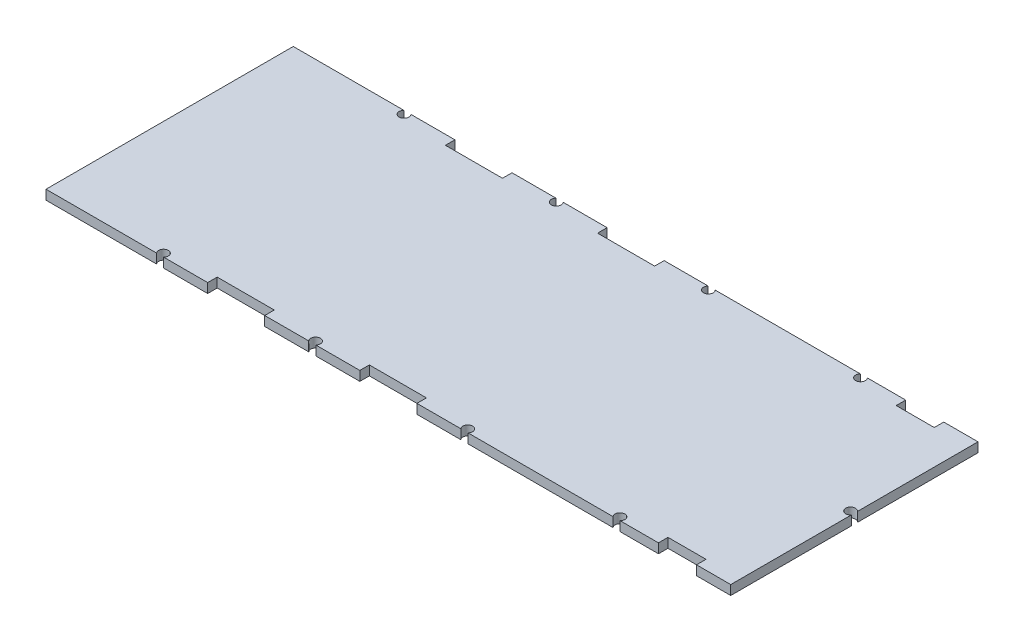
SolidWorks part; units mm, degrees
ref_plane "Front Plane" through (0, 0, 0) normal (0, 0, 1) x (1, 0, 0)
ref_plane "Top Plane" through (0, 0, 0) normal (0, 1, 0) x (1, 0, 0)
ref_plane "Right Plane" through (0, 0, 0) normal (1, 0, 0) x (0, 0, -1)
sketch "Sketch1" plane through (0, 0, 0) normal (0, 1, 0) x (1, 0, 0)
  line L0 (114.3, -1.0072) -> (114.3, -41.275)
  line L1 (-114.3, 41.275) -> (-77.3864, 41.275)
  line L2 (-114.3, 41.275) -> (-114.3, -41.275)
  line L3 (-114.3, -41.275) -> (-77.3864, -41.275)
  line L4 (114.3, 41.275) -> (114.3, 1.0072)
  line L5 (-75.0136, 41.275) -> (-60.325, 41.275)
  line L6 (26.5864, 41.275) -> (75.0136, 41.275)
  line L7 (77.3864, 41.275) -> (89.4932, 41.275)
  line L8 (-24.2136, 41.275) -> (-9.525, 41.275)
  line L9 (-119.8539, 0) -> (200.76, 0) construction
  line L10 (77.3864, -41.275) -> (89.4932, -41.275)
  line L11 (26.5864, -41.275) -> (75.0136, -41.275)
  line L12 (-24.2136, -41.275) -> (-9.525, -41.275)
  line L13 (-75.0136, -41.275) -> (-60.325, -41.275)
  line L14 (-41.275, -41.275) -> (-26.5864, -41.275)
  line L15 (9.525, -41.275) -> (24.2136, -41.275)
  line L16 (-60.325, -41.275) -> (-60.325, -38.1)
  line L17 (-60.325, -38.1) -> (-41.275, -38.1)
  line L18 (-41.275, -41.275) -> (-41.275, -38.1)
  line L19 (-60.325, -43.7685) -> (-41.275, -38.1) construction
  line L20 (-60.325, -38.1) -> (-41.275, -43.7685) construction
  line L21 (102.87, -41.275) -> (114.3, -41.275)
  line L22 (-9.525, -41.275) -> (-9.525, -38.1)
  line L23 (-9.525, -38.1) -> (9.525, -38.1)
  line L24 (9.525, -41.275) -> (9.525, -38.1)
  line L25 (-9.525, -43.7685) -> (9.525, -38.1) construction
  line L26 (-9.525, -38.1) -> (9.525, -43.7685) construction
  line L27 (102.87, 41.275) -> (102.87, 38.1)
  line L28 (89.4932, 41.275) -> (90.17, 41.275)
  line L29 (102.87, 38.1) -> (90.17, 38.1)
  line L30 (102.87, -41.275) -> (102.87, -38.1)
  line L31 (102.87, -38.1) -> (90.17, -38.1)
  line L32 (90.17, -41.275) -> (90.17, -38.1)
  line L33 (90.17, 41.275) -> (90.17, 38.1)
  line L35 (9.525, 41.275) -> (9.525, 38.1)
  line L36 (-9.525, 38.1) -> (9.525, 38.1)
  line L37 (-9.525, 41.275) -> (-9.525, 38.1)
  line L38 (-41.275, 41.275) -> (-41.275, 38.1)
  line L39 (-60.325, 38.1) -> (-41.275, 38.1)
  line L40 (-60.325, 41.275) -> (-60.325, 38.1)
  line L41 (-41.275, 41.275) -> (-26.5864, 41.275)
  line L42 (9.525, 41.275) -> (24.2136, 41.275)
  line L43 (102.87, 41.275) -> (114.3, 41.275)
  line L44 (89.4932, -41.275) -> (90.17, -41.275)
  arc A0 (114.3, 1.0072) -> (114.3, -1.0072) centre (113.024, 0) ccw
  arc A1 (-77.3864, 41.275) -> (-75.0136, 41.275) centre (-76.2, 40.1637) ccw
  arc A2 (-26.5864, 41.275) -> (-24.2136, 41.275) centre (-25.4, 40.1637) ccw
  arc A3 (24.2136, 41.275) -> (26.5864, 41.275) centre (25.4, 40.1637) ccw
  arc A4 (75.0136, 41.275) -> (77.3864, 41.275) centre (76.2, 40.1637) ccw
  arc A5 (75.0136, -41.275) -> (77.3864, -41.275) centre (76.2, -40.1637) cw
  arc A6 (24.2136, -41.275) -> (26.5864, -41.275) centre (25.4, -40.1637) cw
  arc A7 (-26.5864, -41.275) -> (-24.2136, -41.275) centre (-25.4, -40.1637) cw
  arc A8 (-77.3864, -41.275) -> (-75.0136, -41.275) centre (-76.2, -40.1637) cw
  point P34 (-50.8, -40.9342)
  point P39 (0, -40.9342)
  dimension "D5" = 3.2512
  dimension "D6" = 3.2512
  dimension "D7" = 38.1
  dimension "D1" = 228.6
  dimension "D2" = 114.3
  dimension "D4" = 82.55
  dimension "D9" = 19.05
  dimension "D10" = 19.05
  dimension "D11" = 11.43
  dimension "D12" = 3.175
  dimension "D13" = 3.175
  dimension "D14" = 12.7
  dimension "D8" = 4
extrude "Boss-Extrude1" add sketch "Sketch1" along normal blind 3.175
